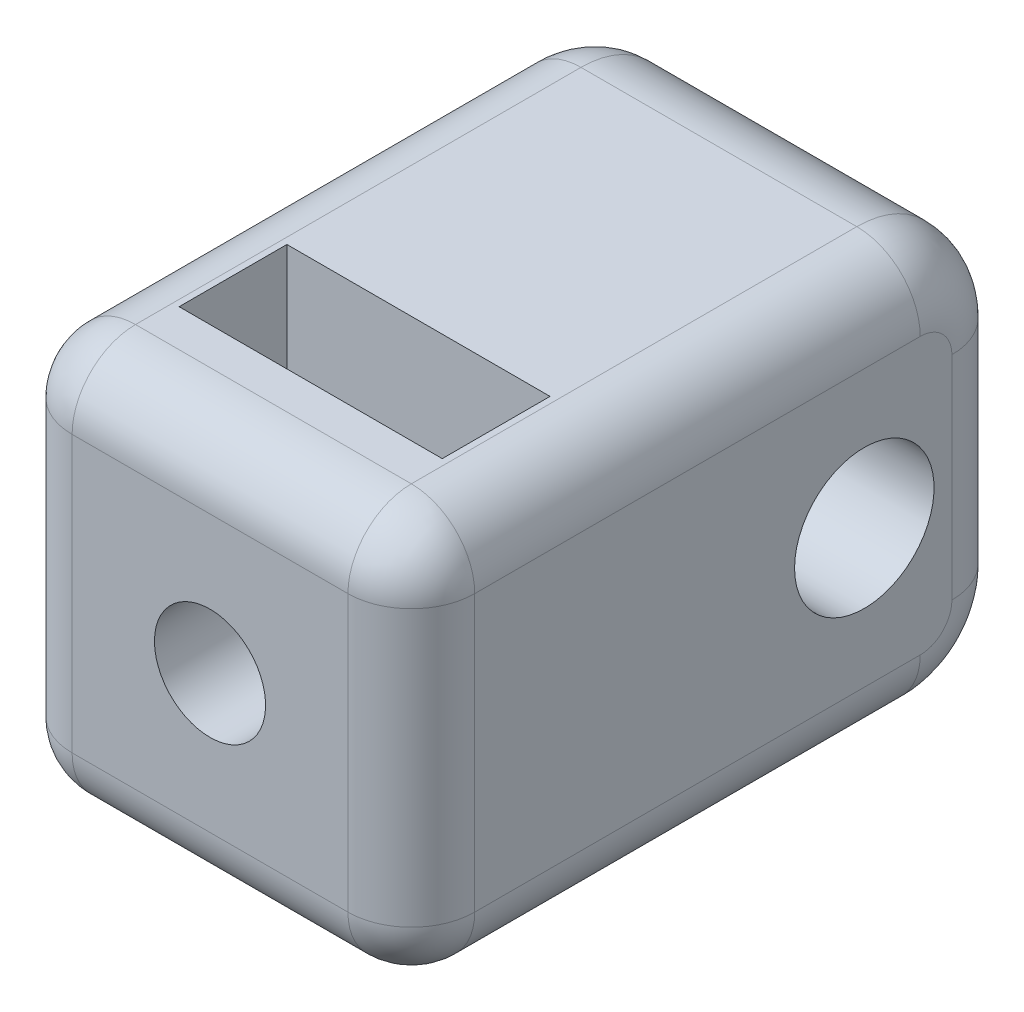
SolidWorks part; units mm, degrees
ref_plane "Front Plane" through (0, 0, 0) normal (0, 0, 1) x (1, 0, 0)
ref_plane "Top Plane" through (0, 0, 0) normal (0, 1, 0) x (1, 0, 0)
ref_plane "Right Plane" through (0, 0, 0) normal (1, 0, 0) x (0, 0, -1)
sketch "Sketch1" plane through (0, 0, 0) normal (0, 1, 0) x (1, 0, 0)
  line L1 (0, 0) -> (-50.8, 0)
  line L2 (0, 0) -> (0, -19.05)
  line L3 (0, -19.05) -> (-50.8, -19.05)
  line L4 (-50.8, 0) -> (-50.8, -19.05)
  dimension "D1" = 19.05
  dimension "D2" = 50.8
extrude "Boss-Extrude1" add sketch "Sketch1" along normal blind 12.7
sketch "Sketch2" plane through (-50.8, 0, 0) normal (-1, 0, 0) x (0, 0, 1)
  line L0 (0, 12.7) -> (0, 0) construction
  circle A0 centre (4.7625, 6.35) radius 2.2
  point P9 (0, 6.35)
  dimension "D1" = 4.4
  dimension "D2" = 4.7625
extrude "Cut-Extrude1" cut sketch "Sketch2" against normal through all
sketch "Sketch3" plane through (0, 12.7, 0) normal (0, 1, 0) x (1, 0, 0)
  line L0 (-50.8, -15.875) -> (0, -15.875) construction
  line L1 (-50.8, 0) -> (-50.8, -19.05) construction
  line L2 (0, -19.05) -> (0, 0) construction
  dimension "D1" = 15.875
ref_plane "Plane1" through (0, 0, 15.875) normal (0, 0, 1) x (1, 0, 0)
sketch "Sketch4" plane through (0, 0, 15.875) normal (0, 0, 1) x (1, 0, 0)
  line L0 (-50.8, 12.7) -> (-50.8, 0) construction
  line L1 (-44.45, 1.558) -> (-40.3, 3.954)
  line L2 (-40.3, 3.954) -> (-40.3, 8.746)
  line L3 (-40.3, 8.746) -> (-44.45, 11.142)
  line L4 (-44.45, 11.142) -> (-48.6, 8.746)
  line L5 (-48.6, 8.746) -> (-48.6, 3.954)
  line L6 (-48.6, 3.954) -> (-44.45, 1.558)
  line L7 (-48.6, 8.746) -> (-48.6, 12.7)
  line L26 (-50.8, 12.7) -> (0, 12.7) construction
  line L27 (-48.6, 12.7) -> (-40.3, 12.7)
  line L28 (-40.3, 12.7) -> (-40.3, 8.746)
  line L29 (-35.9, 8.746) -> (-35.9, 12.7)
  line L30 (-35.9, 8.746) -> (-35.9, 3.954)
  line L31 (-35.9, 3.954) -> (-31.75, 1.558)
  line L32 (-31.75, 1.558) -> (-27.6, 3.954)
  line L33 (-27.6, 3.954) -> (-27.6, 8.746)
  line L34 (-27.6, 12.7) -> (-27.6, 8.746)
  line L35 (-35.9, 12.7) -> (-27.6, 12.7)
  line L36 (-23.2, 8.746) -> (-23.2, 12.7)
  line L37 (-23.2, 8.746) -> (-23.2, 3.954)
  line L38 (-23.2, 3.954) -> (-19.05, 1.558)
  line L39 (-19.05, 1.558) -> (-14.9, 3.954)
  line L40 (-14.9, 3.954) -> (-14.9, 8.746)
  line L41 (-14.9, 12.7) -> (-14.9, 8.746)
  line L42 (-23.2, 12.7) -> (-14.9, 12.7)
  line L43 (-10.5, 8.746) -> (-10.5, 12.7)
  line L44 (-10.5, 8.746) -> (-10.5, 3.954)
  line L45 (-10.5, 3.954) -> (-6.35, 1.558)
  line L46 (-6.35, 1.558) -> (-2.2, 3.954)
  line L47 (-2.2, 3.954) -> (-2.2, 8.746)
  line L48 (-2.2, 12.7) -> (-2.2, 8.746)
  line L49 (-10.5, 12.7) -> (-2.2, 12.7)
  line L50 (-44.45, 6.35) -> (-31.75, 6.35) construction
  circle A0 centre (-44.45, 6.35) radius 4.15 construction
  circle A1 centre (-44.45, 6.35) radius 1.7525
  circle A2 centre (-31.75, 6.35) radius 1.7525
  circle A3 centre (-19.05, 6.35) radius 1.7525
  circle A4 centre (-6.35, 6.35) radius 1.7525
  point P11 (-50.8, 6.35)
  dimension "D2" = 8.3
  dimension "D3" = 3.505
  dimension "D1" = 6.35
  dimension "D4" = 4
  dimension "D5" = 12.7
extrude "Cut-Extrude3" cut sketch "Sketch4" against normal blind 3.4 contours L28 L27 L7 L4 L3 | L5 L6 L1 L2 L3 L4 A1 | L35 L29 L30 L31 L32 L33 L34 A2 | A2 | A1 | A3 | L42 L36 L37 L38 L39 L40 L41 A3 | L49 L43 L44 L45 L46 L47 L48 A4 | A4 region at (-46.4616, 2.8658, 15.875) region at (-44.45, 11.2352, 15.875) region at (-35.7611, 10.723, 15.875) region at (-23.0611, 10.723, 15.875) region at (-10.3611, 10.723, 15.875) region at (-44.45, 6.35, 15.875) region at (-31.75, 6.35, 15.875) region at (-19.05, 6.35, 15.875) region at (-6.35, 6.35, 15.875)
extrude "Cut-Extrude4" cut sketch "Sketch4<3>" against normal blind 3 from surface contours A1 | A2 | A3 | A4 region at (-44.45, 6.35, 15.875) region at (-31.75, 6.35, 15.875) region at (-19.05, 6.35, 15.875) region at (-6.35, 6.35, 15.875) starting at face at (-44.45, 6.9732, 12.475)
sketch "Sketch4<3>" plane through (0, 0, 15.875) normal (0, 0, 1) x (1, 0, 0) same geometry as "Sketch4"
extrude "Cut-Extrude5" cut sketch "Sketch4<4>" along normal up to next contours A1 | A2 | A3 | A4 region at (-44.45, 6.35, 15.875) region at (-31.75, 6.35, 15.875) region at (-19.05, 6.35, 15.875) region at (-6.35, 6.35, 15.875)
sketch "Sketch4<4>" plane through (0, 0, 15.875) normal (0, 0, 1) x (1, 0, 0) same geometry as "Sketch4"
sketch "Sketch5" plane through (0, 12.7, 0) normal (0, 1, 0) x (1, 0, 0)
  line L0 (-50.8, 0) -> (-50.8, -19.05) construction
  line L1 (-38.1, 0) -> (0, 0)
  line L2 (-38.1, 0) -> (-38.1, -19.05)
  line L3 (-38.1, -19.05) -> (0, -19.05)
  line L4 (0, 0) -> (0, -19.05)
  dimension "D1" = 12.7
extrude "Cut-Extrude6" cut sketch "Sketch5" against normal up to next
fillet "Fillet1" radius 3 2 edges at (-44.45, 0, 0) (-44.45, 12.7, 0)
fillet "Fillet2" radius 2 2 edges at (-44.45, 0, 19.05) (-44.45, 12.7, 19.05)
fillet "Fillet3" radius 2 16 edges at (-50.8, 11.8213, 0.8787) (-50.8, 0.8787, 0.8787) (-50.8, 0, 10.025) (-50.8, 0.5858, 18.4642) (-50.8, 6.35, 19.05) (-50.8, 12.1142, 18.4642) (-50.8, 12.7, 10.025) (-50.8, 6.35, 0) (-38.1, 11.8213, 0.8787) (-38.1, 6.35, 0) (-38.1, 0.8787, 0.8787) (-38.1, 0, 10.025) (-38.1, 0.5858, 18.4642) (-38.1, 6.35, 19.05) (-38.1, 12.1142, 18.4642) (-38.1, 12.7, 10.025)
